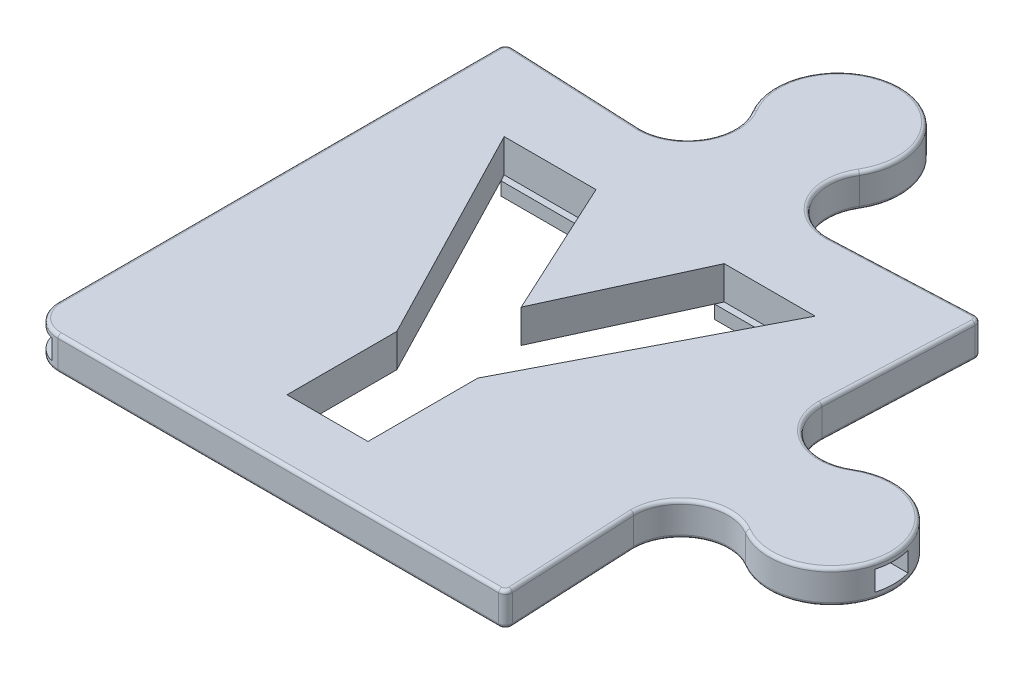
SolidWorks part; units mm, degrees
ref_plane "Front Plane" through (0, 0, 0) normal (0, 0, 1) x (1, 0, 0)
ref_plane "Top Plane" through (0, 0, 0) normal (0, 1, 0) x (1, 0, 0)
ref_plane "Right Plane" through (0, 0, 0) normal (1, 0, 0) x (0, 0, -1)
sketch "Sketch1" plane through (0, 0, 0) normal (0, 1, 0) x (1, 0, 0)
  line L0 (-31, -36) -> (37, -36) construction
  line L1 (-36, 37) -> (-36, -31) construction
  line L2 (-14.1421, 36) -> (-36, 37) construction
  line L3 (37, 37) -> (14.1421, 36) construction
  line L4 (36, 13.1421) -> (37, 37) construction
  line L5 (37, -36) -> (36, -15.1421) construction
  line L6 (-35.4, 36.3719) -> (-35.4, -31)
  line L7 (-36, 36) -> (36, 36) construction
  line L8 (-36, 36) -> (-36, -36) construction
  line L9 (-36, -36) -> (36, -36) construction
  line L10 (36, 36) -> (36, -36) construction
  line L11 (-31, -35.4) -> (36.3705, -35.4)
  line L12 (36.3705, -35.4) -> (35.4, -15.1568)
  line L13 (35.4, 13.155) -> (36.3732, 36.372)
  line L14 (36.3732, 36.372) -> (14.1555, 35.4)
  line L15 (-14.1562, 35.4) -> (-35.4, 36.3719)
  line L16 (-30, -24) -> (30, -24) construction
  line L17 (-30, 29) -> (30, 29) construction
  line L18 (-30, 29) -> (-30, -31) construction
  line L19 (-30, -31) -> (30, -31) construction
  line L20 (30, 29) -> (30, -31) construction
  line L21 (-30, 24) -> (30, 24) construction
  line L22 (-30, 24) -> (-30, -26) construction
  line L23 (-30, -26) -> (30, -26) construction
  line L24 (30, 24) -> (30, -26) construction
  arc A0 (-36, -31) -> (-31, -36) centre (-31, -31) ccw construction
  arc A1 (-14.1421, 36) -> (-8.571, 45.8485) centre (-14.1421, 42.5) ccw construction
  arc A2 (8.571, 45.8485) -> (-8.571, 45.8485) centre (0, 51) ccw construction
  arc A3 (8.571, 45.8485) -> (14.1421, 36) centre (14.1421, 42.5) ccw construction
  arc A4 (36, 13.1421) -> (45.8485, 7.571) centre (42.5, 13.1421) ccw construction
  arc A5 (45.8485, -9.571) -> (45.8485, 7.571) centre (51, -1) ccw construction
  arc A6 (45.8485, -9.571) -> (36, -15.1421) centre (42.5, -15.1421) ccw construction
  arc A7 (-35.4, -31) -> (-31, -35.4) centre (-31, -31) ccw
  arc A8 (46.1576, -9.0567) -> (35.4, -15.1568) centre (42.5, -15.1421) ccw
  arc A9 (46.1576, -9.0567) -> (46.1576, 7.0567) centre (51, -1) ccw
  arc A10 (35.4, 13.155) -> (46.1576, 7.0567) centre (42.5, 13.1421) ccw
  arc A11 (8.0567, 46.1576) -> (14.1555, 35.4) centre (14.1421, 42.5) ccw
  arc A12 (8.0567, 46.1576) -> (-8.0567, 46.1576) centre (0, 51) ccw
  arc A13 (-14.1562, 35.4) -> (-8.0567, 46.1576) centre (-14.1421, 42.5) ccw
  point P32 (36, 0)
  point P34 (0, 36)
  dimension "D5" = 6.5
  dimension "D6" = 10
  dimension "D7" = 6.5
  dimension "D13" = 5
  dimension "D9" = 10
  dimension "D11" = 6.5
  dimension "D12" = 6.5
  dimension "D1" = 72
  dimension "D2" = 1
  dimension "D3" = 1
  dimension "D4" = 15
  dimension "D8" = 1
  dimension "D10" = 35
  dimension "D14" = 15
  dimension "D15" = 36
  dimension "D16" = 1
  dimension "D18" = 60
  dimension "D19" = 60
  dimension "D20" = 5
  dimension "D21" = 6
  dimension "D22" = 5
  dimension "D23" = 50
  dimension "D24" = 2
  dimension "D17" = 0.6
extrude "Boss-Extrude1" add sketch "Sketch1" along normal blind 5
sketch "Sketch6" plane through (0, 0, 0) normal (0, -1, 0) x (1, 0, 0)
  line L0 (-35.4, -36.3719) -> (-35.4, 31) construction
  line L1 (-35.4, 17.9) -> (-27.4, 17.9)
  line L2 (-35.4, 17.9) -> (-35.4, -16.1)
  line L3 (-35.4, -16.1) -> (-27.4, -16.1)
  line L4 (-27.4, 17.9) -> (-27.4, -16.1)
  line L5 (-31, 35.4) -> (36.3705, 35.4) construction
  line L6 (-35.4, 14.65) -> (-30.4, 14.65)
  line L7 (-35.4, 14.65) -> (-35.4, -12.85)
  line L8 (-35.4, -12.85) -> (-30.4, -12.85)
  line L9 (-30.4, 14.65) -> (-30.4, -12.85)
  point P15 (-27.4, 0.9)
  point P16 (-30.4, 0.9)
  line M28 (-35.4, 31) -> (-35.4, -36.3719)
  dimension "D1" = 8
  dimension "D2" = 20.75
  dimension "D3" = 27.5
  dimension "D4" = 5
  dimension "D5" = 34
extrude "Cut-Extrude3" cut sketch "Sketch6" against normal blind 3 from offset 1 contours L6 L9 L8 L3 L4 L1 M28 | L9 L6 L2 L8 region at (-29.8665, 0, 0.9) region at (-32.9, 0, 0.9) offset against normal yes
extrude "Cut-Extrude4" cut sketch "Sketch6<3>" against normal up to next contours L9 L6 L2 L8 region at (-32.9, 0, 0.9)
sketch "Sketch6<3>" plane through (0, 0, 0) normal (0, -1, 0) x (1, 0, 0) same geometry as "Sketch6"
sketch "Sketch8" plane through (0, 0, 0) normal (0, -1, 0) x (1, 0, 0)
  line L1 (-2.5, -51.4) -> (2.5, -51.4)
  line L2 (-2.5, -51.4) -> (-2.5, -60.4)
  line L3 (-2.5, -60.4) -> (2.5, -60.4)
  line L4 (2.5, -51.4) -> (2.5, -60.4)
  line L5 (51.4, 3.5) -> (60.4, 3.5)
  line L6 (51.4, 3.5) -> (51.4, -1.5)
  line L7 (51.4, -1.5) -> (60.4, -1.5)
  line L8 (60.4, 3.5) -> (60.4, -1.5)
  arc A0 (-8.0567, -46.1576) -> (8.0567, -46.1576) centre (0, -51) ccw construction
  arc A1 (46.1576, -7.0567) -> (46.1576, 9.0567) centre (51, 1) ccw construction
  point P4 (0, -60.4)
  point P13 (60.4, 1)
  dimension "D1" = 5
  dimension "D2" = 9
  dimension "D3" = 5
  dimension "D4" = 9
extrude "Cut-Extrude5" cut sketch "Sketch8" against normal blind 3 from offset 1 offset against normal yes
sketch "Sketch9" plane through (0, 0, 0) normal (0, -1, 0) x (1, 0, 0)
  line L0 (-31, 35.4) -> (36.3705, 35.4) construction
  line L1 (-35.4, 14.65) -> (-35.4, 31) construction
  line L2 (-31.7636, 35.3332) -> (-35.4, 31) construction
  line L3 (-33.2571, 29.735) -> (-30.0429, 33.565) construction
  line L4 (-30.0429, 33.565) -> (-33.2571, 29.735) construction
  line L5 (-30.0429, 33.565) -> (-32.7119, 35.8048)
  line L6 (-33.2571, 29.735) -> (-35.926, 31.9747)
  line L7 (-32.7119, 35.8048) -> (-35.926, 31.9747)
  circle A0 centre (-31.65, 31.65) radius 2.5
  arc A1 (-31, 35.4) -> (-35.4, 31) centre (-31, 31) ccw construction
  arc M41 (-31, 35.4) -> (-35.4, 31) centre (-31, 31) ccw
  dimension "D1" = 5
  dimension "D3" = 3.75
  dimension "D4" = 5.6569
  dimension "D2" = 3.75
extrude "Cut-Extrude6" cut sketch "Sketch9" against normal blind 3 from offset 1 contours A0 L5 L6 M41 | A0 L5 region at (-33.6239, 0, 33.3064) region at (-31.65, 0, 31.65) offset against normal yes
sketch "Sketch11" plane through (-35.4, 0, 0) normal (-1, 0, 0) x (0, 0, 1)
  line L0 (-13.155, 0) -> (-36.372, 0) construction
  line L1 (-25.1, 3) -> (-19.1, 3)
  line L2 (-25.1, 3) -> (-25.1, 1.5)
  line L3 (-25.1, 1.5) -> (-19.1, 1.5)
  line L4 (-19.1, 3) -> (-19.1, 1.5)
  line L5 (-16.1, 4) -> (-16.1, 1) construction
  line L6 (35.4, 0) -> (15.1568, 0) construction
  line L7 (20.9, 3) -> (26.9, 3)
  line L8 (20.9, 3) -> (20.9, 1.5)
  line L9 (20.9, 1.5) -> (26.9, 1.5)
  line L10 (26.9, 3) -> (26.9, 1.5)
  line L12 (17.9, 4) -> (17.9, 1) construction
  dimension "D1" = 3
  dimension "D2" = 1.5
  dimension "D3" = 3
  dimension "D4" = 6
  dimension "D5" = 3
  dimension "D6" = 1.5
  dimension "D7" = 6
  dimension "D8" = 3
fillet "Fillet1" radius 0.5 17 edges at (-35.4, 0, 22.825) (-34.1113, 0, 34.1113) (2.6853, 0, 35.4) (35.8853, 0, 25.2784) (38.9978, 0, 8.966) (60.4, 0, 1) (38.9986, 0, -6.9655) (35.8866, 0, -24.7635) (25.2643, 0, -35.886) (7.9657, 0, -38.9984) (0, 0, -60.4) (-7.9658, 0, -38.9981) (-24.7781, 0, -35.886) (-35.4, 0, -24.611) (-32.9, 0, -12.85) (-30.4, 0, 0.9) (-32.9, 0, 14.65)
fillet "Fillet2" radius 0.5 13 edges at (-7.9658, 5, -38.9981) (0, 5, -60.4) (7.9657, 5, -38.9984) (25.2643, 5, -35.886) (35.8866, 5, -24.7635) (38.9986, 5, -6.9655) (60.4, 5, 1) (38.9978, 5, 8.966) (35.8853, 5, 25.2784) (2.6853, 5, 35.4) (-34.1113, 5, 34.1113) (-35.4, 5, -2.686) (-24.7781, 5, -35.886)
fillet "Fillet3" radius 1 9 edges at (36.2202, 0.1464, -36.2187) (36.2202, 4.8536, -36.2187) (36.3732, 2.5, -36.372) (-35.2536, 0.1464, -36.2186) (-35.2536, 4.8536, -36.2186) (36.2169, 0.1464, 35.2536) (36.2169, 4.8536, 35.2536) (36.3705, 2.5, 35.4) (-35.4, 2.5, -36.3719)
extrude "Cut-Extrude9" cut sketch "Sketch11" against normal blind 3
chamfer "Chamfer1" distance 1 angle 50 2 edges at (-35.4, 1.5, 23.9) (-35.4, 1.5, -22.1) first distance on face at (-35.4, 2.25, -22.1)
sketch "Sketch12" plane through (0, 5, 0) normal (0, 1, 0) x (1, 0, 0)
  text T0 "Y" font "Poppins" height 50
extrude "Cut-Extrude10" cut sketch "Sketch12" against normal through all
sketch "Sketch13" plane through (0, 0, 0) normal (0, -1, 0) x (1, 0, 0)
  line L0 (6.2448, 9.4707) -> (6.2448, 26) construction
  line L1 (-5.9357, 26) -> (6.2448, 26)
  line L2 (-5.9357, 26) -> (-5.9357, 25)
  line L3 (-5.9357, 25) -> (6.2448, 25)
  line L4 (6.2448, 26) -> (6.2448, 25)
  line L5 (0.2576, -3.0602) -> (9.8722, -24) construction
  line L6 (9.4131, -23) -> (23.5573, -23)
  line L7 (9.4131, -23) -> (9.4131, -24)
  line L8 (9.4131, -24) -> (23.5573, -24)
  line L9 (23.5573, -23) -> (23.5573, -24)
  line L10 (-9.4291, -24) -> (0.2576, -3.0602) construction
  line L11 (-8.9665, -23) -> (-23.2481, -23)
  line L12 (-8.9665, -23) -> (-8.9665, -24)
  line L13 (-8.9665, -24) -> (-23.2481, -24)
  line L14 (-23.2481, -23) -> (-23.2481, -24)
  line M24 (23.5573, -24) -> (9.8722, -24)
  line M25 (9.8722, -24) -> (0.2576, -3.0602)
  line M26 (0.2576, -3.0602) -> (-9.4291, -24)
  line M27 (-9.4291, -24) -> (-23.2481, -24)
  line M28 (-23.2481, -24) -> (-5.9357, 9.4707)
  line M29 (-5.9357, 9.4707) -> (-5.9357, 26)
  line M30 (-5.9357, 26) -> (6.2448, 26)
  line M31 (6.2448, 26) -> (6.2448, 9.4707)
  line M32 (6.2448, 9.4707) -> (23.5573, -24)
  dimension "D1" = 1
  dimension "D2" = 1
  dimension "D3" = 1
extrude "Boss-Extrude3" add sketch "Sketch13" along normal blind 2 separate body contours L11 M26 M28 M27 | L6 M25 M24 M32 | L3 M29 M31 M30 region at (0.1546, 0, 25.5) region at (-16.0938, 0, -23.5003) region at (16.4708, 0, -23.5004)
